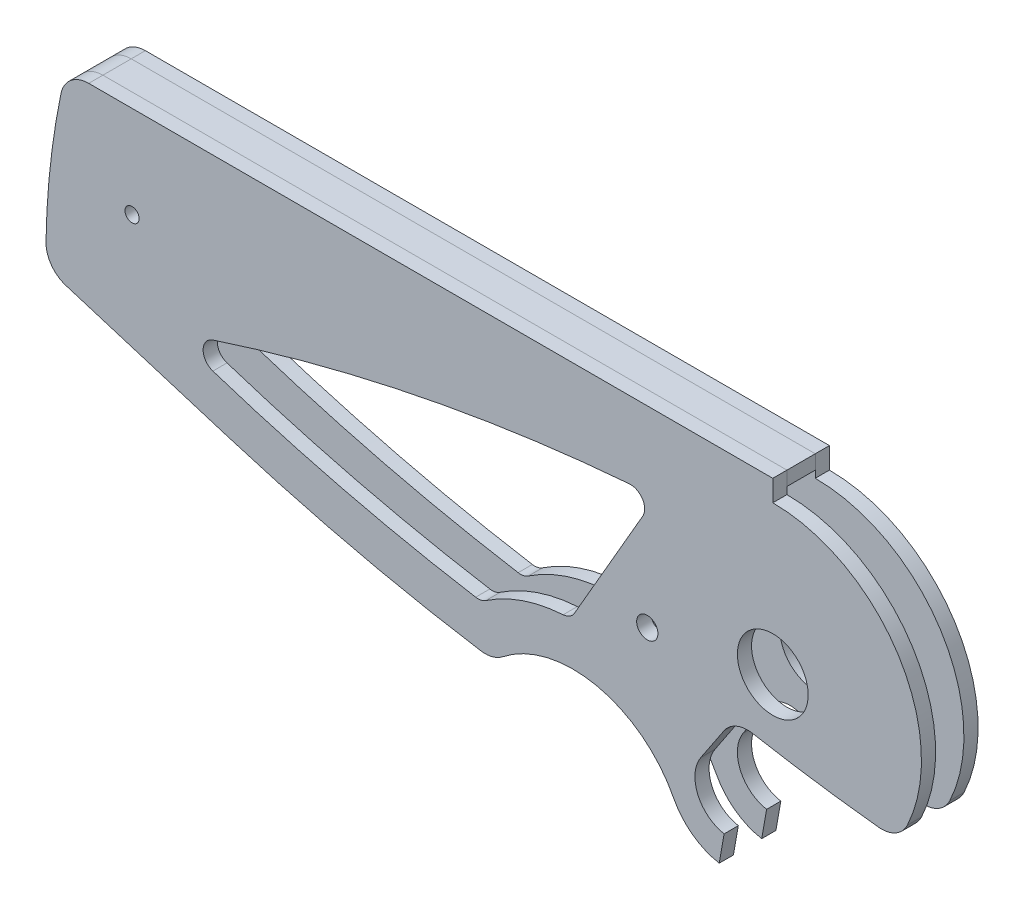
SolidWorks part; units mm, degrees
material "Obyčejná uhlíková ocel"
ref_plane "Přední rovina" through (0, 0, 0) normal (0, 0, 1) x (1, 0, 0)
ref_plane "Horní rovina" through (0, 0, 0) normal (0, 1, 0) x (1, 0, 0)
ref_plane "Pravá rovina" through (0, 0, 0) normal (1, 0, 0) x (0, 0, -1)
sketch "Skica15" plane through (0, 0, 0) normal (0, 0, 1) x (1, 0, 0)
  line L0 (0, 10) -> (0, -10)
  line L1 (0, 0) -> (-50, 0) construction
  line L2 (-1.7365, -9.8481) -> (1.7365, 9.8481)
  line L3 (0, 0) -> (49.2404, -8.6824) construction
  arc A0 (-50, 0) -> (0, 10) centre (0, -120) cw
  arc A1 (-50, 0) -> (0, -10) centre (0, 120) ccw
  arc A2 (1.7365, 9.8481) -> (49.2404, -8.6824) centre (-20.8378, -118.1769) cw
  arc A3 (-1.7365, -9.8481) -> (49.2404, -8.6824) centre (20.8378, 118.1769) ccw
  circle A4 centre (0, 0) radius 10
  dimension "D2" = 130
  dimension "D1" = 20
  dimension "D3" = 50
  dimension "D4" = 10
ref_plane "Rovina2" through (0, 0, 1) normal (0, 0, 1) x (1, 0, 0)
sketch "Skica1" plane through (0, 0, 1) normal (0, 0, 1) x (1, 0, 0)
  line L1 (-3.4519, -5.1731) -> (-5.0795, -7.6124)
  line L2 (0, 0) -> (-59.5409, 0) construction
  line L3 (-3, -9) -> (-3, -17.0212) construction
  line L4 (-3.4341, -11.462) -> (-3.7814, -13.4316)
  line L5 (-49.9157, -1.1721) -> (-38.4483, -4.7076)
  line L6 (0, 10.5) -> (0, 12)
  line L7 (0, 12) -> (-48.3078, 12)
  circle A0 centre (0, 0) radius 2.5
  arc A1 (9.5026, -4.4665) -> (0, 10.5) centre (0, 0) ccw
  arc A2 (7.478, -5.6042) -> (-1.4305, -4.3154) centre (20.8378, 118.1769) cw
  arc A3 (-5.0795, -7.6124) -> (-3.4341, -11.462) centre (-3, -9) ccw
  arc A4 (-7, -11.0616) -> (-3.7814, -13.4316) centre (-3, -9) ccw
  arc A5 (7.478, -5.6042) -> (9.5026, -4.4665) centre (7.6926, -3.6157) ccw
  arc A6 (-50.2663, 10.4054) -> (-51.3262, 0.7691) centre (0, 0) ccw
  arc A7 (-1.7365, -9.8481) -> (49.2404, -8.6824) centre (20.8378, 118.1769) ccw construction
  arc A8 (-7, -11.0616) -> (-19.0746, -8.4525) centre (-14.1111, -14.7265) ccw
  arc A9 (-51.3262, 0.7691) -> (-49.9157, -1.1721) centre (-49.3265, 0.7391) ccw
  arc A10 (-20.6316, -8.8588) -> (-38.4483, -4.7076) centre (0, 120) cw
  circle A11 centre (-50, 0) radius 1 construction
  arc A12 (-20.6316, -8.8588) -> (-19.0746, -8.4525) centre (-20.3154, -6.8839) ccw
  arc A13 (-50, 0) -> (0, -10) centre (0, 120) ccw construction
  arc A14 (-1.4305, -4.3154) -> (-3.4519, -5.1731) centre (-1.7882, -6.2832) ccw
  arc A15 (-48.3078, 12) -> (-50.2663, 10.4054) centre (-48.3078, 10) ccw
  point P34 (-19.7017, -9.0042)
  dimension "D1" = 5
  dimension "D2" = 10.5
  dimension "D3" = 2
  dimension "D4" = 5
  dimension "D5" = 3
  dimension "D6" = 9
  dimension "D7" = 2
  dimension "D10" = 2
  dimension "D11" = 2
  dimension "D13" = 2
  dimension "D14" = 12
  dimension "D12" = 2
  dimension "D9" = 0.5
  dimension "D16" = 8
  dimension "D17" = 1.5
  dimension "D19" = 2
  dimension "D15" = 2
  dimension "D8" = 10
  dimension "D18" = 7
extrude "Přidat vysunutím1" add sketch "Skica1" along normal blind 1
sketch "Skica2" plane through (0, 0, 0) normal (0, 0, 1) x (1, 0, 0)
  line L0 (-8.8633, -1.5628) -> (0, 0) construction
  line L2 (0, 0) -> (-50, 0) construction
  circle A0 centre (-8.8633, -1.5628) radius 0.75
  circle A1 centre (-45.2466, 5.5) radius 0.5
  dimension "D3" = 1.5
  dimension "D5" = 1
  dimension "D8" = 5.5
  dimension "D1" = 10
  dimension "D2" = 9
  dimension "D7" = 45.2466
sketch "Skica14" plane through (0, 0, 0) normal (0, 0, 1) x (1, 0, 0)
  line L0 (-14.001, -3.2504) -> (-9.1805, 5.0988)
  line L1 (0, 0) -> (-50, 0) construction
  arc A0 (-39.5409, -1.2137) -> (-20.9819, -5.7617) centre (0, 120) ccw
  arc A1 (-39.5422, 0.6873) -> (-10.1263, 6.5956) centre (0, -120) cw
  arc A2 (-38.4483, -4.7076) -> (-20.6316, -8.8588) centre (0, 120) ccw construction
  circle A3 centre (0, 0) radius 10 construction
  arc A4 (-39.5422, 0.6873) -> (-39.5409, -1.2137) centre (-39.2308, -0.263) ccw
  arc A5 (-20.2585, -5.6046) -> (-20.9819, -5.7617) centre (-20.8174, -4.7753) cw
  arc A6 (-9.1805, 5.0988) -> (-10.1263, 6.5956) centre (-10.0466, 5.5988) ccw
  arc A7 (0, 10) -> (-50, 0) centre (0, -120) ccw construction
  arc A8 (-20.2585, -5.6046) -> (-14.804, -3.7484) centre (-14.1111, -14.7265) cw
  arc A10 (-14.804, -3.7484) -> (-14.001, -3.2504) centre (-14.867, -2.7504) ccw
  arc A11 (-38.4483, -4.7076) -> (-20.6316, -8.8588) centre (0, 120) ccw construction
  arc A13 (-7, -11.0616) -> (-19.0746, -8.4525) centre (-14.1111, -14.7265) ccw construction
  dimension "D2" = 3
  dimension "D3" = 2
  dimension "D4" = 3
  dimension "D5" = 3
  dimension "D6" = 0.5
  dimension "D1" = 60
extrude "Odebrat vysunutím3" cut sketch "Skica14" along normal through all
extrude "Odebrat vysunutím2" cut sketch "Skica2" along normal through all
sketch "Skica16" plane through (0, 0, 0) normal (0, 0, -1) x (-1, 0, 0)
  line L0 (0, 12) -> (48.3078, 12) construction
  line L1 (0, 10.5) -> (0, 12) construction
  line L2 (0, 12) -> (48.3078, 12)
  line L3 (0, 11) -> (0, 12)
  arc A0 (51.3262, 0.7691) -> (50.2663, 10.4054) centre (0, 0) ccw construction
  arc A1 (49.9157, -1.1721) -> (51.3262, 0.7691) centre (49.3265, 0.7391) ccw construction
  arc A2 (50.2663, 10.4054) -> (48.3078, 12) centre (48.3078, 10) ccw construction
  arc A3 (51.3262, 0.7691) -> (50.2663, 10.4054) centre (0, 0) ccw
  arc A4 (51.3156, 0.531) -> (51.3262, 0.7691) centre (49.3265, 0.7391) ccw
  arc A5 (50.2663, 10.4054) -> (48.3078, 12) centre (48.3078, 10) ccw
  arc A13 (50.3846, 0.9231) -> (0, 11) centre (0, -120) ccw
  arc A14 (51.3156, 0.531) -> (0, 11) centre (0, -120) ccw
  dimension "D1" = 1
extrude "Přidat vysunutím2" add sketch "Skica16" along normal mid plane 2 separate body
mirror "Zrcadlit1" about plane through (0, 0, 0) normal (0, 0, 1) of bodies 119
